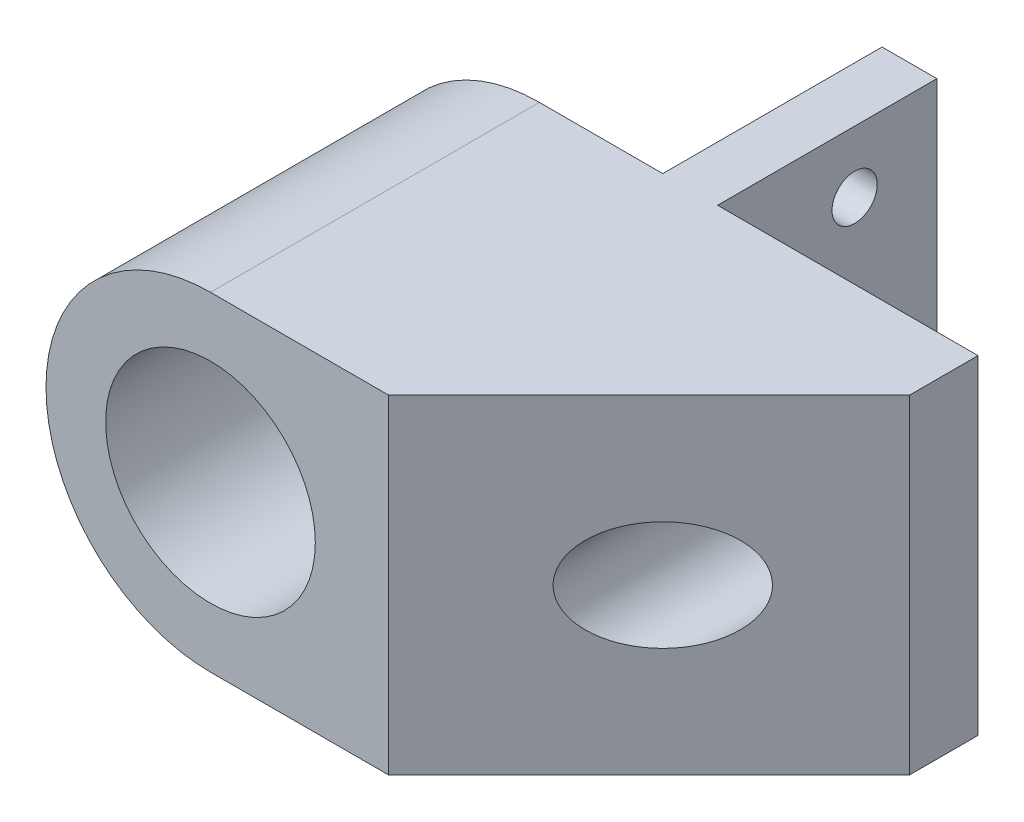
SolidWorks part; units mm, degrees
ref_plane "Plano frontal" through (0, 0, 0) normal (0, 0, 1) x (1, 0, 0)
ref_plane "Plano superior" through (0, 0, 0) normal (0, 1, 0) x (1, 0, 0)
ref_plane "Plano direito" through (0, 0, 0) normal (1, 0, 0) x (0, 0, -1)
sketch "Esboço1" plane through (0, 0, 0) normal (0, 0, 1) x (1, 0, 0)
  line L0 (0, 0) -> (-19, 0)
  line L1 (-23, 0) -> (-23, 6)
  line L2 (-32, -24) -> (-23, -24)
  line L3 (0, -24) -> (0, 0)
  line L4 (-23, 6) -> (-19, 6)
  line L5 (-19, 6) -> (-19, 0)
  line L6 (-32, -12) -> (-24.5731, -12) construction
  line L7 (-19, -30) -> (-19, -24)
  line L8 (-23, -30) -> (-19, -30)
  line L9 (-23, -24) -> (-23, -30)
  line L10 (-23, 0) -> (-32, 0)
  line L11 (-19, -24) -> (0, -24)
  arc A0 (-32, 0) -> (-32, -24) centre (-32, -12) ccw
  circle A1 centre (-32, -12) radius 7.65
  circle A2 centre (-9, -12) radius 1.6
  point P10 (0, -12)
  dimension "D1" = 15.3
  dimension "D5" = 3.2
  dimension "D2" = 32
  dimension "D3" = 24
  dimension "D4" = 9
  dimension "D6" = 10
  dimension "D7" = 6
  dimension "D8" = 4
extrude "Ressalto-extrusão1" add sketch "Esboço1" along normal blind 40
sketch "Esboço2" plane through (0, 0, 0) normal (0, 1, 0) x (1, 0, 0)
  line L1 (0, -40) -> (-19, -40)
  line L2 (0, -40) -> (0, -20)
  line L3 (0, -20) -> (-19, -20)
  line L4 (-19, -40) -> (-19, -20)
  line L6 (-23, -40) -> (-23, 0) construction
  line L7 (-44, 0) -> (-23, 0)
  line L8 (-44, 0) -> (-44, -16)
  line L9 (-44, -16) -> (-23, -16)
  line L10 (-23, 0) -> (-23, -16)
  line L11 (0, 0) -> (-19, 0)
  line L12 (0, 0) -> (0, -16)
  line L13 (0, -16) -> (-19, -16)
  line L14 (-19, 0) -> (-19, -16)
  line L15 (-19, -40) -> (-19, 0) construction
  line L16 (-19, -40) -> (-19, 0) construction
  line L17 (-44, -40) -> (-32, -40) construction
  dimension "D1" = 24
  dimension "D3" = 4
extrude "Corte-extrusão1" cut sketch "Esboço2" against normal through all
sketch "Esboço3" plane through (-23, 0, 0) normal (-1, 0, 0) x (0, 0, 1)
  line L0 (0, -12) -> (16, -12) construction
  line L1 (0, 6) -> (0, -30) construction
  line L2 (16, -24) -> (16, 0) construction
  line L3 (0, -16) -> (16, -16) construction
  line L4 (0, -8) -> (16, -8) construction
  line L6 (0, 6) -> (40, 6)
  line L7 (0, 6) -> (0, 0)
  line L8 (0, 0) -> (40, 0)
  line L9 (40, 6) -> (40, 0)
  line L10 (40, -24) -> (0, -24)
  line L11 (40, -24) -> (40, -30)
  line L12 (40, -30) -> (0, -30)
  line L13 (0, -24) -> (0, -30)
  circle A0 centre (6, -4.5) radius 1.65
  circle A1 centre (6, -19.5) radius 1.65
  dimension "D3" = 3.3
  dimension "D4" = 15
  dimension "D5" = 10
  dimension "D1" = 4
  dimension "D2" = 4
extrude "Corte-extrusão2" cut sketch "Esboço3" against normal blind 20
chamfer "Chanfro2" distance 20 angle 45 1 edges at (-19, -12, 20)
sketch "Esboço4" plane through (0, 0, 40) normal (0, 0, 1) x (1, 0, 0)
  circle A0 centre (-9, -12) radius 4
  dimension "D1" = 8
extrude "Corte-extrusão3" cut sketch "Esboço4" against normal up to vertex (19 mm away) up to point (0, 0, 21)
